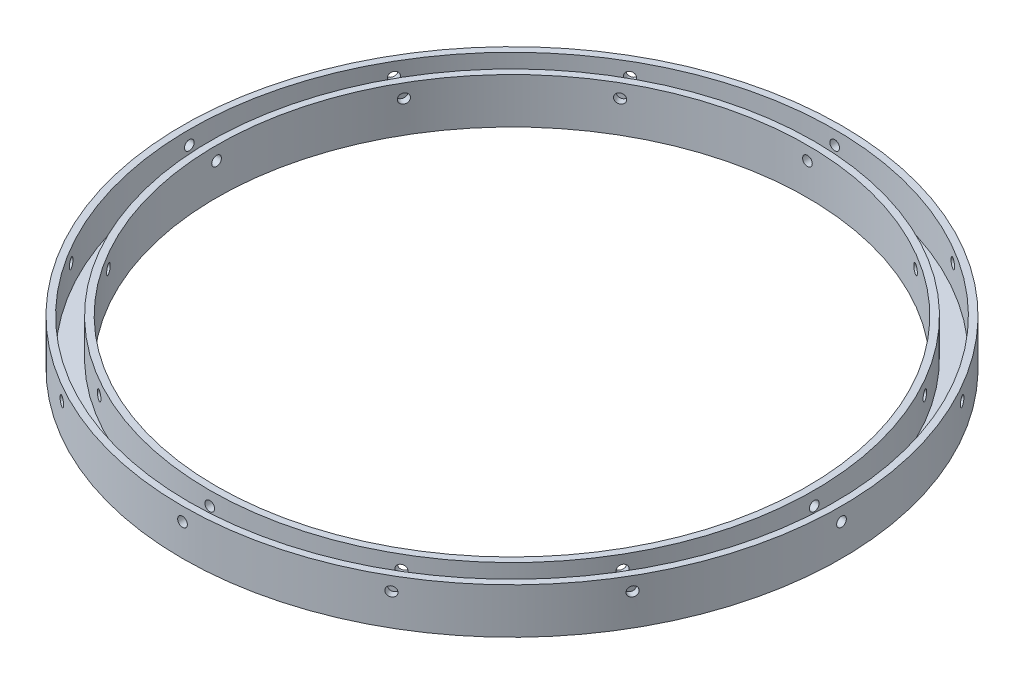
SolidWorks part; units mm, degrees
ref_plane "Front Plane" through (0, 0, 0) normal (0, 0, 1) x (1, 0, 0)
ref_plane "Top Plane" through (0, 0, 0) normal (0, 1, 0) x (1, 0, 0)
ref_plane "Right Plane" through (0, 0, 0) normal (1, 0, 0) x (0, 0, -1)
sketch "Sketch1" plane through (0, 0, 0) normal (0, 1, 0) x (1, 0, 0)
  circle A0 centre (0, 0) radius 92.075
  circle A1 centre (0, 0) radius 82.55
  dimension "D1" = 184.15
  dimension "D2" = 165.1
extrude "Boss-Extrude1" add sketch "Sketch1" along normal blind 12.7
sketch "Sketch2" plane through (0, 12.7, 0) normal (0, 1, 0) x (1, 0, 0)
  circle A0 centre (0, 0) radius 84.455
  circle A1 centre (0, 0) radius 90.17
  dimension "D1" = 180.34
  dimension "D2" = 168.91
extrude "Cut-Extrude1" cut sketch "Sketch2" against normal blind 10.16
sketch "Sketch3" plane through (0, 0, 0) normal (0, 0, 1) x (1, 0, 0)
  line L0 (92.075, 12.7) -> (-92.075, 12.7) construction
  circle A0 centre (0, 8.89) radius 1.3525
  point P2 (-0.7669, -11.1084)
  point P3 (0, 0)
  point P7 (0, 0)
  dimension "D1" = 2.7051
  dimension "D2" = 3.81
extrude "Cut-Extrude2" cut sketch "Sketch3" against normal up to surface (92.0651 mm away) up to face at (0, 12.7, 92.075)
pattern_circular "CirPattern1" count 12 over 360 about axis through (0, 12.7, 0) along (0, 1, 0) of "Cut-Extrude2"
